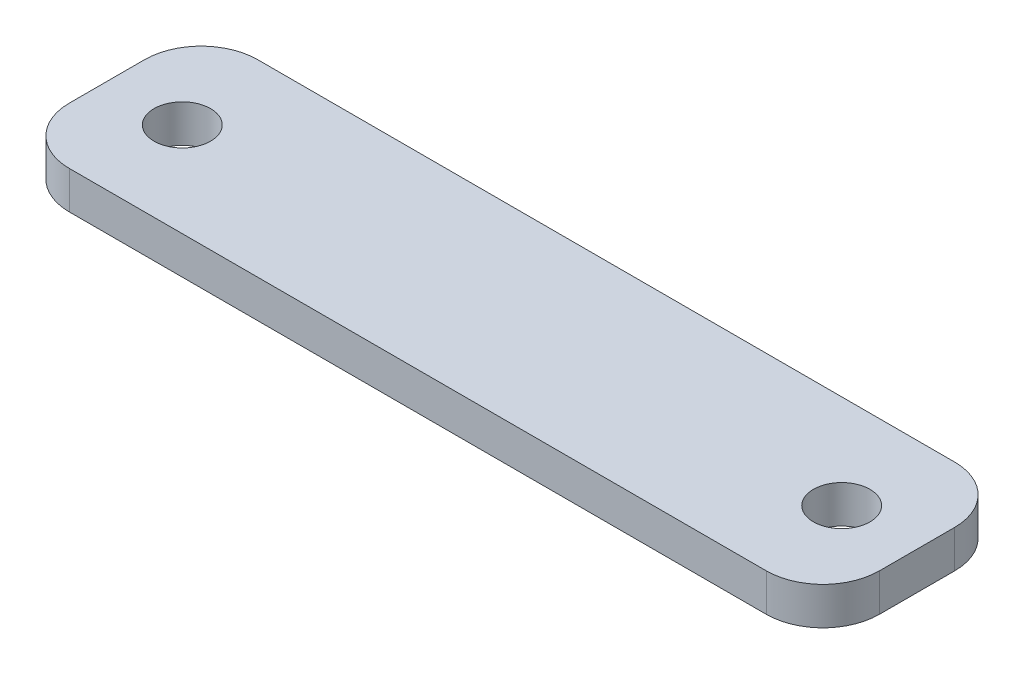
SolidWorks part; units mm, degrees
ref_plane "Front Plane" through (0, 0, 0) normal (0, 0, 1) x (1, 0, 0)
ref_plane "Top Plane" through (0, 0, 0) normal (0, 1, 0) x (1, 0, 0)
ref_plane "Right Plane" through (0, 0, 0) normal (1, 0, 0) x (0, 0, -1)
sketch "Sketch1" plane through (0, 0, 0) normal (0, 1, 0) x (1, 0, 0)
  line L1 (-21.5, 5) -> (21.5, 5)
  line L2 (-21.5, 5) -> (-21.5, -5)
  line L3 (-21.5, -5) -> (21.5, -5)
  line L4 (21.5, 5) -> (21.5, -5)
  line L5 (-21.5, 5) -> (21.5, -5) construction
  line L6 (-21.5, -5) -> (21.5, 5) construction
  point P0 (0, 0)
  dimension "D1" = 10
  dimension "D2" = 43
extrude "Boss-Extrude1" add sketch "Sketch1" along normal blind 2
sketch "Sketch2" plane through (0, 2, 0) normal (0, 1, 0) x (1, 0, 0)
  point P10 (26.3156, 0)
fillet "Fillet1" radius 3 4 edges at (21.5, 1, 5) (21.5, 1, -5) (-21.5, 1, 5) (-21.5, 1, -5)
hole_wizard "Ø3.0mm Dowel Hole1" positions "Sketch5" profile "Sketch6" hole size "Ø3.0" standard "ISO" end condition through all
sketch "Sketch5" plane through (0, 0, 0) normal (0, -1, 0) x (-1, 0, 0)
  line L1 (-21.5, -2) -> (-21.5, 2) construction
  line L3 (21.5, 0) -> (-21.5, 0) construction
  line L4 (21.5, 2) -> (21.5, -2) construction
  line L5 (21.5, 2) -> (21.5, -2) construction
  point P0 (-17.5, 0)
  point P2 (17.5, 0)
  point P22 (0, 0)
  point P23 (0, 0)
  point P24 (0, 0)
  point P25 (0, 0)
  point P26 (0, 0)
  point P27 (0, 0)
  point P28 (0, 0)
  dimension "D1" = 4
  dimension "D2" = 35
sketch "Sketch6" plane through (17.5, 0, 0) normal (1, 0, 0) x (0, 0, -1)
  line L0 (0, 0) -> (0, 2)
  line L1 (0, 2) -> (1.5, 2)
  line L2 (1.5, 2) -> (1.5, 0)
  line L5 (1.5, 0) -> (0, 0)
  line L11 (0, -6.35) -> (0, 107.95) construction
  dimension "Thru Hole Dia." = 3
  dimension "Thru Hole Depth" = 2
equation "\"globalength1\"=55"
